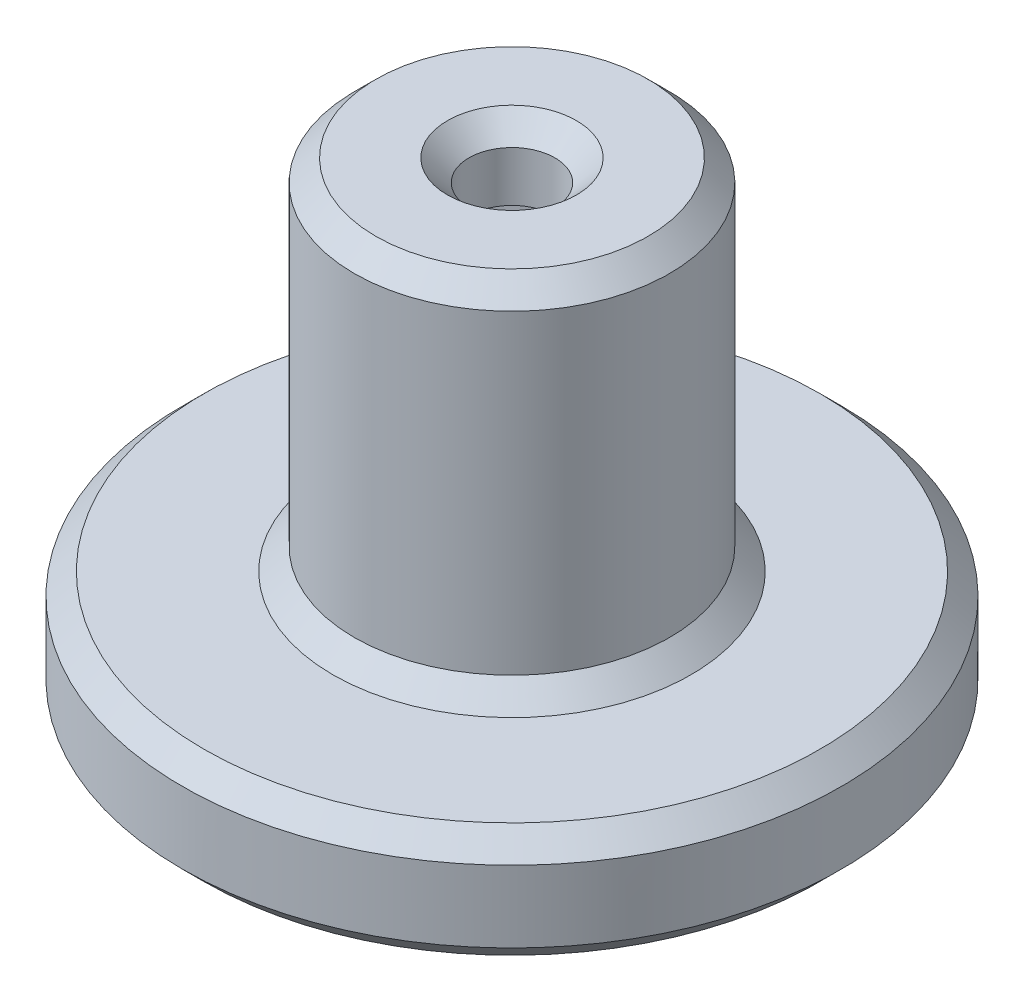
SolidWorks part; units mm, degrees
ref_plane "Front Plane" through (0, 0, 0) normal (0, 0, 1) x (1, 0, 0)
ref_plane "Top Plane" through (0, 0, 0) normal (0, 1, 0) x (1, 0, 0)
ref_plane "Right Plane" through (0, 0, 0) normal (1, 0, 0) x (0, 0, -1)
sketch "Sketch1" plane through (0, 0, 0) normal (0, 1, 0) x (1, 0, 0)
  line L1 (5.65, -7.212) -> (5.65, -0.688)
  line L2 (5.65, -0.688) -> (0, 2.5741)
  line L3 (0, 2.5741) -> (-5.65, -0.688)
  line L4 (-5.65, -0.688) -> (-5.65, -7.212)
  line L5 (-5.65, -7.212) -> (0, -10.4741)
  line L6 (0, -10.4741) -> (5.65, -7.212)
  line L7 (17.5, -5.2) -> (-17.5, -5.2)
  line L8 (17.5, -5.2) -> (17.5, -2.7)
  line L9 (17.5, -2.7) -> (-17.5, -2.7)
  line L10 (-17.5, -5.2) -> (-17.5, -2.7)
  line L11 (17.5, -5.2) -> (-17.5, -2.7) construction
  line L12 (17.5, -2.7) -> (-17.5, -5.2) construction
  circle A0 centre (0, 0) radius 19.05 construction
  circle A1 centre (0, -3.95) radius 23
  circle A2 centre (0, -3.95) radius 11
  circle A3 centre (0, -3.95) radius 5.65 construction
  circle A4 centre (0, -3.95) radius 3
  dimension "D1" = 38.1
  dimension "D2" = 46
  dimension "D3" = 22
  dimension "D4" = 11.3
  dimension "D5" = 6
  dimension "D6" = 2.5
  dimension "D7" = 35
extrude "Boss-Extrude1" add sketch "Sketch1" along normal blind 8 contours A1 A2 | A2 L6 L5 L4 L3 L2 L1 | L7 A2 L1 L6 L5 L4 | A2 L9 L10 L7 | A2 L7 L8 L9 | L7 A2 L9 L1 | L9 A2 L7 L4 region at (5.8893, 0, 6.206) region at (8.3132, 0, 3.95) region at (5.8893, 0, 1.694) region at (14.2381, 0, 3.95) region at (-8.3132, 0, 3.95) region at (-14.2381, 0, 3.95) region at (-22.3495, 0, 3.95)
extrude "Cut-Extrude1" cut sketch "Sketch1<4>" along normal blind 3.5 contours A2 L9 L10 L7 | L9 A2 L7 L4 | L7 A2 L9 L1 | A2 L7 L8 L9 region at (8.3132, 0, 3.95) region at (14.2381, 0, 3.95) region at (-8.3132, 0, 3.95) region at (-14.2381, 0, 3.95)
sketch "Sketch1<4>" plane through (0, 0, 0) normal (0, 1, 0) x (1, 0, 0) same geometry as "Sketch1"
extrude "Boss-Extrude2" add sketch "Sketch1<5>" along normal blind 20 from surface contours L7 A2 L1 L6 L5 L4 | L9 A2 L4 L3 L2 L1 | L9 A2 L7 L4 | L7 A2 L9 L1 region at (5.8893, 0, 6.206) region at (8.3132, 0, 3.95) region at (5.8893, 0, 1.694) region at (-8.3132, 0, 3.95) starting at face at (0, 8, 3.95)
sketch "Sketch1<5>" plane through (0, 0, 0) normal (0, 1, 0) x (1, 0, 0) same geometry as "Sketch1"
extrude "Boss-Extrude3" add sketch "Sketch1<6>" along normal blind 5 from surface contours L7 A2 L1 L6 L5 L4 | A4 L7 L4 L5 L6 L1 | A4 L9 L1 L2 L3 L4 | L9 A2 L4 L3 L2 L1 | L7 A2 L9 L1 | L9 A2 L7 L4 | A4 L7 L1 L9 | A4 L9 L4 L7 region at (0, 0, 7.3876) region at (5.8893, 0, 6.206) region at (4.2792, 0, 3.95) region at (8.3132, 0, 3.95) region at (0, 0, 0.5124) region at (5.8893, 0, 1.694) region at (-8.3132, 0, 3.95) region at (-4.2792, 0, 3.95) starting at face at (0, 28, 3.95)
sketch "Sketch1<6>" plane through (0, 0, 0) normal (0, 1, 0) x (1, 0, 0) same geometry as "Sketch1"
chamfer "Chamfer1" distance 1.5 angle 45 13 edges at (-5.65, 0, 6.206) (-2.825, 0, 8.843) (2.825, 0, 8.843) (5.65, 0, 6.206) (-5.65, 0, 1.694) (5.65, 0, 1.694) (-2.825, 0, -0.943) (2.825, 0, -0.943) (0, 0, 26.95) (0, 8, 26.95) (0, 8, 14.95) (0, 33, 6.95) (0, 33, 14.95)
